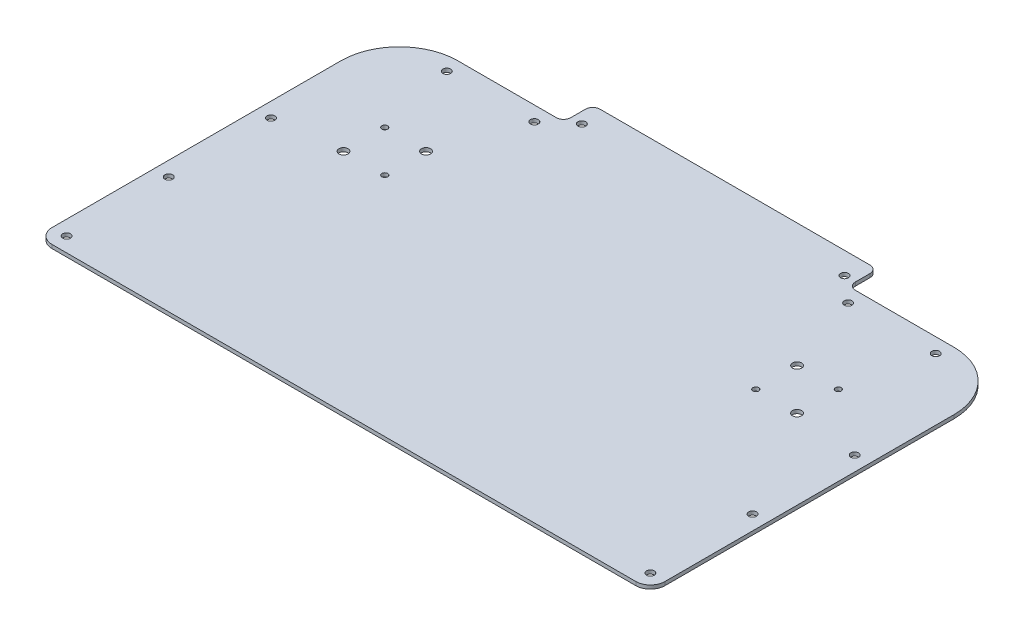
SolidWorks part; units mm, degrees
material "6061-T6 (SS)"
ref_plane "Front Plane" through (0, 0, 0) normal (0, 0, 1) x (1, 0, 0)
ref_plane "Top Plane" through (0, 0, 0) normal (0, 1, 0) x (1, 0, 0)
ref_plane "Right Plane" through (0, 0, 0) normal (1, 0, 0) x (0, 0, -1)
sketch "Sketch2" plane through (0, 0, 0) normal (0, 1, 0) x (1, 0, 0)
  line L1 (-266.7, -25.4) -> (-266.7, -340.36)
  line L2 (-266.7, -340.36) -> (266.7, -340.36)
  line L3 (266.7, -340.36) -> (266.7, -25.4)
  line L5 (123.825, -25.4) -> (266.7, -25.4)
  line L6 (-123.825, -25.4) -> (-123.825, 0)
  line L7 (-123.825, 0) -> (123.825, 0)
  line L8 (123.825, 0) -> (123.825, -25.4)
  line L10 (-123.825, -25.4) -> (-266.7, -25.4)
  line L11 (-266.7, -149.86) -> (-123.825, -25.4) construction
  line L12 (123.825, -25.4) -> (266.7, -149.86) construction
  point P4 (0, 0)
  point P12 (0, -340.36)
  point P14 (0, 0)
  dimension "D5" = 190.5
  dimension "D1" = 142.875
  dimension "D2" = 533.4
  dimension "D3" = 340.36
  dimension "D4" = 190.5
  dimension "D7" = 25.4
extrude "Boss-Extrude1" add sketch "Sketch2" along normal blind 3.175
sketch "Sketch3" plane through (0, 3.175, 0) normal (0, 1, 0) x (1, 0, 0)
  line L0 (-123.825, 0) -> (-123.825, -25.4) construction
  line L1 (123.825, -25.4) -> (123.825, 0) construction
  line L2 (123.825, 0) -> (-123.825, 0) construction
  circle A0 centre (-114.3, -19.05) radius 3.3782
  circle A1 centre (114.3, -19.05) radius 3.3782
  dimension "D4" = 6.7564
  dimension "D1" = 9.525
  dimension "D2" = 9.525
  dimension "D3" = 19.05
extrude "Cut-Extrude1" cut sketch "Sketch3" against normal through all
sketch "Sketch4" plane through (0, 3.175, 0) normal (0, 1, 0) x (1, 0, 0)
  arc A0 (-195.8278, -147.0391) -> (-198.8682, -139.707) centre (-197.348, -143.373) ccw construction
  arc A1 (-195.8278, -147.0391) -> (-198.8682, -139.707) centre (-197.348, -143.373) ccw
  arc A2 (-161.427, -145.9257) -> (-161.427, -140.8203) centre (-161.427, -143.373) ccw construction
  arc A3 (-161.427, -140.8203) -> (-161.427, -145.9257) centre (-161.427, -143.373) ccw construction
  arc A4 (-197.348, -110.0047) -> (-197.348, -104.8993) centre (-197.348, -107.452) ccw construction
  arc A5 (-197.348, -104.8993) -> (-197.348, -110.0047) centre (-197.348, -107.452) ccw construction
  arc A6 (-159.9068, -111.118) -> (-162.9472, -103.7859) centre (-161.427, -107.452) ccw construction
  arc A7 (-162.9472, -103.7859) -> (-159.9068, -111.118) centre (-161.427, -107.452) ccw construction
  arc A8 (-161.427, -145.9257) -> (-161.427, -140.8203) centre (-161.427, -143.373) ccw
  arc A9 (-161.427, -140.8203) -> (-161.427, -145.9257) centre (-161.427, -143.373) ccw
  arc A10 (-197.348, -110.0047) -> (-197.348, -104.8993) centre (-197.348, -107.452) ccw
  arc A11 (-197.348, -104.8993) -> (-197.348, -110.0047) centre (-197.348, -107.452) ccw
  arc A12 (-159.9068, -111.118) -> (-162.9472, -103.7859) centre (-161.427, -107.452) ccw
  arc A13 (-162.9472, -103.7859) -> (-159.9068, -111.118) centre (-161.427, -107.452) ccw
  arc A14 (-198.8682, -139.707) -> (-195.8278, -147.0391) centre (-197.348, -143.373) ccw construction
  arc A15 (-198.8682, -139.707) -> (-195.8278, -147.0391) centre (-197.348, -143.373) ccw
extrude "Cut-Extrude2" cut sketch "Sketch4" against normal through all
sketch "Sketch6" plane through (0, 3.175, 0) normal (0, 1, 0) x (1, 0, 0)
  arc A0 (201.0141, -141.8528) -> (193.682, -144.8932) centre (197.348, -143.373) ccw construction
  arc A1 (193.682, -144.8932) -> (201.0141, -141.8528) centre (197.348, -143.373) ccw construction
  arc A2 (157.7609, -108.9722) -> (165.093, -105.9318) centre (161.427, -107.452) ccw construction
  arc A3 (165.093, -105.9318) -> (157.7609, -108.9722) centre (161.427, -107.452) ccw construction
  arc A4 (199.9007, -107.452) -> (194.7953, -107.452) centre (197.348, -107.452) ccw construction
  arc A5 (194.7953, -107.452) -> (199.9007, -107.452) centre (197.348, -107.452) ccw construction
  arc A6 (158.8743, -143.373) -> (163.9797, -143.373) centre (161.427, -143.373) ccw construction
  arc A7 (163.9797, -143.373) -> (158.8743, -143.373) centre (161.427, -143.373) ccw construction
  arc A8 (201.0141, -141.8528) -> (193.682, -144.8932) centre (197.348, -143.373) ccw
  arc A9 (193.682, -144.8932) -> (201.0141, -141.8528) centre (197.348, -143.373) ccw
  arc A10 (157.7609, -108.9722) -> (165.093, -105.9318) centre (161.427, -107.452) ccw
  arc A11 (165.093, -105.9318) -> (157.7609, -108.9722) centre (161.427, -107.452) ccw
  arc A12 (199.9007, -107.452) -> (194.7953, -107.452) centre (197.348, -107.452) ccw
  arc A13 (194.7953, -107.452) -> (199.9007, -107.452) centre (197.348, -107.452) ccw
  arc A14 (158.8743, -143.373) -> (163.9797, -143.373) centre (161.427, -143.373) ccw
  arc A15 (163.9797, -143.373) -> (158.8743, -143.373) centre (161.427, -143.373) ccw
extrude "Cut-Extrude3" cut sketch "Sketch6" against normal through all
sketch "Sketch8" [suppressed] plane through (0, 3.175, 0) normal (0, 1, 0) x (1, 0, 0)
  line L0 (123.825, 0) -> (-123.825, 0) construction
  line L1 (-7.9375, -44.45) -> (7.9375, -44.45)
  line L2 (-7.9375, -44.45) -> (-7.9375, -171.45)
  line L3 (-7.9375, -171.45) -> (7.9375, -171.45)
  line L4 (7.9375, -44.45) -> (7.9375, -171.45)
  point P4 (0, -44.45)
  dimension "D1" = 15.875
  dimension "D2" = 127
  dimension "D3" = 44.45
extrude "Cut-Extrude5" [suppressed] cut sketch "Sketch8" against normal through all
fillet "Fillet1" radius 50.8 2 edges at (-266.7, 1.5875, 25.4) (266.7, 1.5875, 25.4)
fillet "Fillet2" radius 6.35 2 edges at (-123.825, 1.5875, 25.4) (123.825, 1.5875, 25.4)
fillet "Fillet3" radius 12.7 2 edges at (266.7, 1.5875, 340.36) (-266.7, 1.5875, 340.36)
fillet "Fillet4" radius 6.35 2 edges at (123.825, 1.5875, 0) (-123.825, 1.5875, 0)
sketch "Sketch7" plane through (0, 3.175, 0) normal (0, 1, 0) x (1, 0, 0)
  line L0 (0, 0) -> (0, -340.36) construction
  line L1 (-254, -340.36) -> (254, -340.36) construction
  line L2 (-266.7, -76.2) -> (-266.7, -327.66) construction
  line L3 (-130.175, -25.4) -> (-215.9, -25.4) construction
  line L5 (-123.825, -6.35) -> (-123.825, -19.05) construction
  circle A0 centre (-254, -327.66) radius 3.3782
  circle A1 centre (-254, -238.76) radius 3.3782
  circle A2 centre (-254, -149.86) radius 3.3782
  circle A4 centre (-136.525, -38.1) radius 3.3782
  circle A7 centre (-212.725, -38.1) radius 3.3782
  circle A8 centre (254, -327.66) radius 3.3782
  circle A9 centre (254, -238.76) radius 3.3782
  circle A10 centre (254, -149.86) radius 3.3782
  circle A11 centre (212.725, -38.1) radius 3.3782
  circle A12 centre (136.525, -38.1) radius 3.3782
  dimension "D1" = 6.7564
  dimension "D9" = 6.7564
  dimension "D2" = 12.7
  dimension "D3" = 12.7
  dimension "D4" = 88.9
  dimension "D5" = 88.9
  dimension "D6" = 12.7
  dimension "D7" = 12.7
  dimension "D8" = 76.2
extrude "Cut-Extrude4" cut sketch "Sketch7" against normal through all
